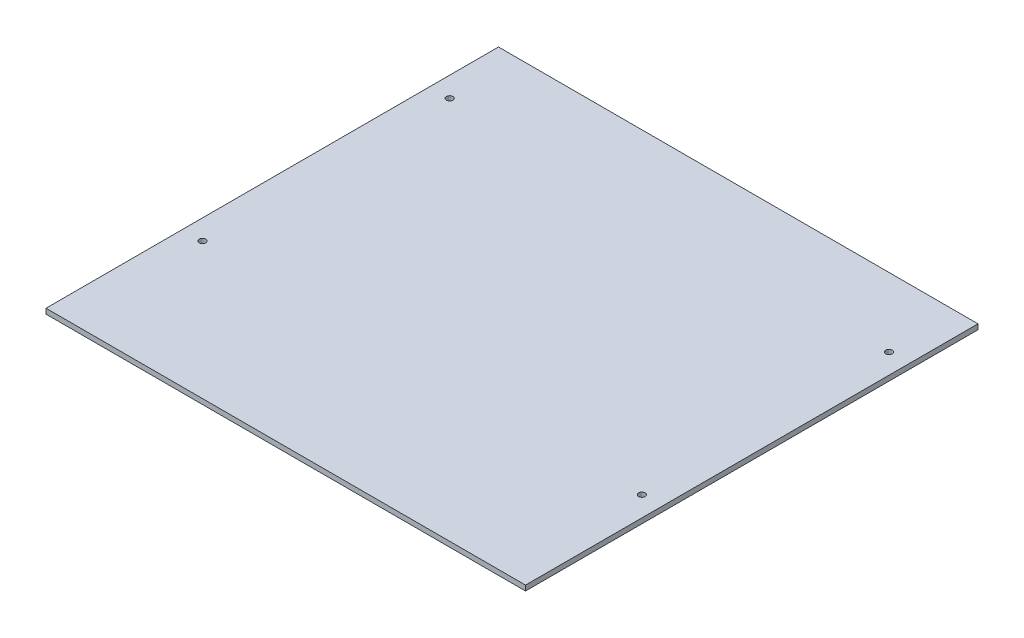
SolidWorks part; units mm, degrees
ref_plane "Front" through (0, 0, 0) normal (0, 0, 1) x (1, 0, 0)
ref_plane "Top" through (0, 0, 0) normal (0, 1, 0) x (1, 0, 0)
ref_plane "Right" through (0, 0, 0) normal (1, 0, 0) x (0, 0, -1)
ref_axis "side-side" through (80.9, 0, 0) along (-1, 0, 0)
ref_axis "up-down" through (0, 50, 0) along (0, -1, 0)
ref_axis "front-back" through (0, 0, -80.9) along (0, 0, 1)
sketch "Sketch1" plane through (0, 0, 0) normal (0, 1, 0) x (1, 0, 0)
  line L0 (0, 0) -> (0, -40.132) construction
  line L1 (-139.7, 0) -> (139.7, 0)
  line L2 (-139.7, 0) -> (-139.7, -263.652)
  line L3 (-139.7, -263.652) -> (139.7, -263.652)
  line L4 (139.7, 0) -> (139.7, -263.652)
  line L5 (-128, -40.132) -> (128, -40.132) construction
  line L6 (-128, -40.132) -> (-128, -184.132) construction
  line L7 (-128, -184.132) -> (128, -184.132) construction
  line L8 (128, -40.132) -> (128, -184.132) construction
  circle A0 centre (-128, -40.132) radius 1.8923
  circle A1 centre (128, -40.132) radius 1.8923
  circle A2 centre (-128, -184.132) radius 1.8923
  circle A3 centre (128, -184.132) radius 1.8923
  dimension "D3" = 40.132
  dimension "D7" = 3.7846
  dimension "D1" = 279.4
  dimension "D2" = 263.652
  dimension "D4" = 256
  dimension "D5" = 11.7
  dimension "D6" = 144
extrude "Boss-Extrude1" add sketch "Sketch1" along normal blind 3
